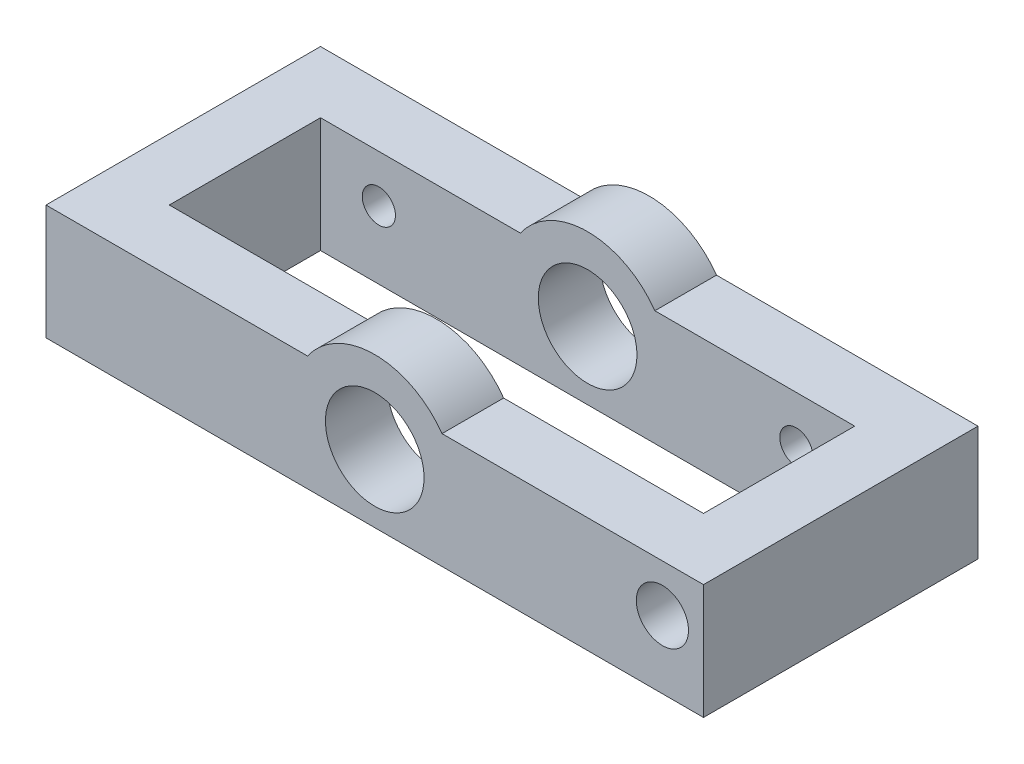
SolidWorks part; units mm, degrees
ref_plane "Front" through (0, 0, 0) normal (0, 0, 1) x (1, 0, 0)
ref_plane "Top" through (0, 0, 0) normal (0, 1, 0) x (1, 0, 0)
ref_plane "Right" through (0, 0, 0) normal (1, 0, 0) x (0, 0, -1)
sketch "Sketch1" plane through (0, 0, 0) normal (0, 1, 0) x (1, 0, 0)
  line L1 (0, 0) -> (65, 0)
  line L2 (0, 0) -> (0, 18.4)
  line L3 (0, 18.4) -> (65, 18.4)
  line L4 (65, 0) -> (65, 18.4)
  line L5 (0, 25.9) -> (72.5, 25.9)
  line L6 (72.5, 25.9) -> (72.5, -7.5)
  line L7 (72.5, -7.5) -> (-7.5, -7.5)
  line L8 (-7.5, -7.5) -> (-7.5, 25.9)
  line L9 (-7.5, 25.9) -> (0, 25.9)
  dimension "D1" = 65
  dimension "D2" = 18.4
  dimension "D3" = 7.5
  dimension "D4" = 72.5
  dimension "D5" = 33.4
  dimension "D6" = 80
extrude "Boss-Extrude1" add sketch "Sketch1" along normal blind 7.5
sketch "Sketch2" plane through (0, 0, 7.5) normal (0, 0, 1) x (1, 0, 0)
  line L0 (32.5, 7.5) -> (32.5, 0)
  line L1 (-7.5, 7.5) -> (72.5, 7.5) construction
  line L2 (-7.5, 0) -> (72.5, 0) construction
  circle A0 centre (32.5, 3.75) radius 10
extrude "Boss-Extrude2" add sketch "Sketch2" against normal blind 7.5 contours A0
sketch "Sketch3" plane through (0, 0, 7.5) normal (0, 0, 1) x (1, 0, 0)
  line L0 (23.2298, 7.5) -> (41.7702, 0)
  circle A0 centre (32.5, 3.75) radius 6
extrude "Cut-Extrude1" cut sketch "Sketch3" against normal blind 7.5 contours L0 A0 | L0 A0 region at (33.4549, 6.1106, 7.5) region at (31.5451, 1.3894, 7.5)
sketch "Sketch4" plane through (0, 0, -25.9) normal (0, 0, -1) x (-1, 0, 0)
  line L0 (-32.5, 7.5) -> (-32.5, 0)
  line L1 (-72.5, 7.5) -> (7.5, 7.5) construction
  line L2 (-72.5, 0) -> (7.5, 0) construction
  circle A0 centre (-32.5, 3.75) radius 10
  line M1 (-72.5, 0) -> (7.5, 0)
  line M3 (7.5, 7.5) -> (-72.5, 7.5)
extrude "Boss-Extrude3" add sketch "Sketch4" against normal blind 7.5 contours A0 M1 | A0 M3 | A0 L0 M3 M1 | A0 L0 M1 M3 region at (27.6174, 3.75, -25.9) region at (32.5, 10.082, -25.9) region at (37.3826, 3.75, -25.9) region at (32.5, -2.582, -25.9)
sketch "Sketch5" plane through (0, 0, -25.9) normal (0, 0, -1) x (-1, 0, 0)
  line L0 (-41.7702, 7.5) -> (-23.2298, 0)
  circle A0 centre (-32.5, 3.75) radius 6
extrude "Cut-Extrude2" cut sketch "Sketch5" against normal blind 7.5 contours L0 A0 | L0 A0 region at (31.5451, 6.1106, -25.9) region at (33.4549, 1.3894, -25.9)
sketch "Sketch6" plane through (0, 0, -25.9) normal (0, 0, -1) x (-1, 0, 0)
  line L0 (-32.5, 3.75) -> (-7.1, 3.75)
  line L1 (-32.5, 3.75) -> (-57.9, 3.75)
  circle A0 centre (-7.1, 3.75) radius 2.0193
  circle A1 centre (-57.9, 3.75) radius 2.0193
  circle A2 centre (-100.1247, -36.9451) radius 2.0193
  dimension "D1" = 25.4
  dimension "D2" = 25.4
extrude "Cut-Extrude3" cut sketch "Sketch6" against normal blind 7.5 contours A0 | A1 region at (7.1, 5.7122, -25.9)
sketch "Sketch8" plane through (0, 0, 0) normal (0, -1, 0) x (-1, 0, 0)
  line L0 (-72.5, 25.9) -> (-65, 18.4)
  line L1 (-65, 0) -> (-72.5, -7.5)
  line L2 (7.5, 25.9) -> (0, 18.4)
  line L3 (7.5, -7.5) -> (0, 0)
  circle A0 centre (3.75, 22.15) radius 1.6875
  circle A1 centre (3.75, -3.75) radius 1.6875
  circle A2 centre (-68.75, -3.75) radius 1.6875
  circle A3 centre (-68.75, 22.15) radius 1.6875
sketch "Sketch11" plane through (0, 0, -25.9) normal (0, 0, -1) x (-1, 0, 0)
  line L0 (-72.5, 0) -> (-67.5, 0)
  line L1 (-72.5, 7.5) -> (-72.5, 0) construction
  line L2 (-72.5, 3.75) -> (-67.5, 3.75)
  line L3 (-72.5, 7.5) -> (-72.5, 0) construction
  circle A2 centre (-67.5, 3.75) radius 3.175
  dimension "D1" = 5
extrude "Cut-Extrude6" cut sketch "Sketch11" against normal through all contours A2
extrude "Boss-Extrude6" add sketch "Sketch1<4>" against normal blind 6.5
sketch "Sketch1<4>" plane through (0, 0, 0) normal (0, 1, 0) x (1, 0, 0) same geometry as "Sketch1"
extrude "Cut-Extrude7" cut sketch "Sketch3<4>" against normal through all contours L0 A0 | L0 A0 region at (33.4549, 6.1106, 7.5) region at (31.5451, 1.3894, 7.5)
sketch "Sketch3<4>" plane through (0, 0, 7.5) normal (0, 0, 1) x (1, 0, 0) same geometry as "Sketch3"
sketch "Sketch13" plane through (0, -6.5, 0) normal (0, -1, 0) x (1, 0, 0)
  line L1 (72.5, -25.9) -> (-7.5, -25.9)
  line L2 (72.5, -25.9) -> (72.5, 7.5)
  line L3 (72.5, 7.5) -> (-7.5, 7.5)
  line L4 (-7.5, -25.9) -> (-7.5, 7.5)
extrude "Cut-Extrude8" cut sketch "Sketch13" against normal blind 2
sketch "Sketch14" plane through (0, 7.5, 0) normal (0, 1, 0) x (1, 0, 0)
  line L1 (72.5, -7.5) -> (-7.5, -7.5)
  line L2 (72.5, -7.5) -> (72.5, 25.9)
  line L3 (72.5, 25.9) -> (-7.5, 25.9)
  line L4 (-7.5, -7.5) -> (-7.5, 25.9)
  line L5 (65, 0) -> (0, 0)
  line L6 (65, 0) -> (65, 18.4)
  line L7 (65, 18.4) -> (0, 18.4)
  line L8 (0, 0) -> (0, 18.4)
extrude "Boss-Extrude7" add sketch "Sketch14" along normal blind 2
extrude "Cut-Extrude9" cut sketch "Sketch3<5>" against normal through all contours L0 A0 | L0 A0 region at (33.4549, 6.1106, 7.5) region at (31.5451, 1.3894, 7.5)
sketch "Sketch3<5>" plane through (0, 0, 7.5) normal (0, 0, 1) x (1, 0, 0) same geometry as "Sketch3"
